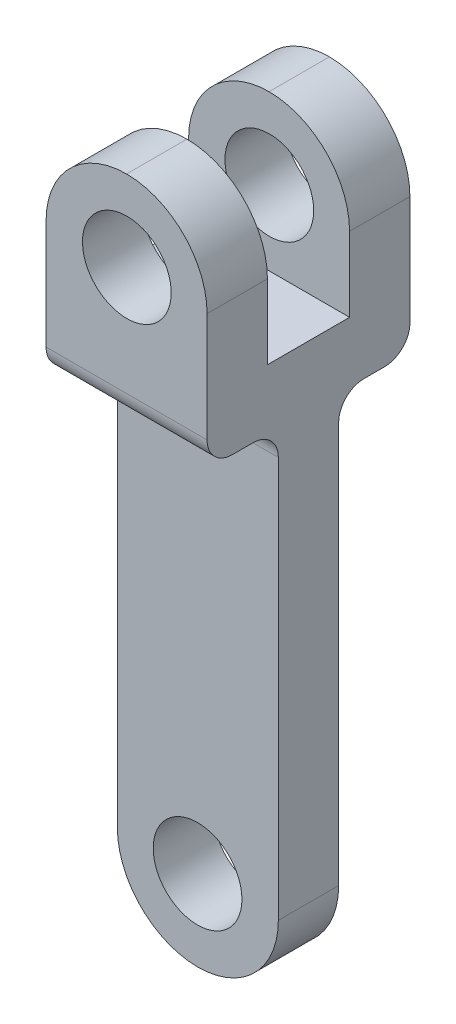
SolidWorks part; units mm, degrees
material "Alumina"
ref_plane "Plano frontal" through (0, 0, 0) normal (0, 0, 1) x (1, 0, 0)
ref_plane "Plano superior" through (0, 0, 0) normal (0, 1, 0) x (1, 0, 0)
ref_plane "Plano direito" through (0, 0, 0) normal (1, 0, 0) x (0, 0, -1)
sketch "Esboço2" plane through (0, 0, 0) normal (1, 0, 0) x (0, 0, -1)
  line L0 (8, 17) -> (8, 0)
  line L1 (8, 0) -> (-8, 0)
  line L2 (0, 0) -> (0, 13.3613) construction
  line L3 (-8, 17) -> (-8, 0)
  dimension "D1" = 17
  dimension "D2" = 8
extrude "Extrusão-Fina1" add sketch "Esboço2" along normal mid plane 12.7 thin thin type one direction reverse wall 4.76
fillet "Filete1" radius 6.37 4 edges at (-6.35, 17, -5.62) (-6.35, 17, 5.62) (6.35, 17, 5.62) (6.35, 17, -5.62)
sketch "Esboço3" plane through (0, 0, -8) normal (0, 0, -1) x (-1, 0, 0)
  circle A0 centre (-0.02, 10.63) radius 3.5
  dimension "D1" = 7
extrude "Corte-extrusão1" cut sketch "Esboço3" against normal through all
sketch "Esboço4" plane through (0, 0, 0) normal (0, -1, 0) x (1, 0, 0)
  line L0 (-6.35, 0) -> (6.35, 0)
  line L1 (-6.35, 8) -> (-6.35, -8) construction
  line L2 (6.35, 8) -> (6.35, -8) construction
extrude "Extrusão-Fina2" add sketch "Esboço4" along normal blind 40 thin thin type mid plane wall 4.76
fillet "Filete2" radius 6.37 2 edges at (-6.35, -40, 0) (6.35, -40, 0)
sketch "Esboço5" plane through (0, 0, 2.38) normal (0, 0, 1) x (1, 0, 0)
  circle A0 centre (-0.02, -33.63) radius 3.5
  dimension "D1" = 7
extrude "Corte-extrusão2" cut sketch "Esboço5" against normal through all
fillet "Filete4" radius 2 4 edges at (0, 0, 2.38) (0, 0, 8) (0, 0, -2.38) (0, 0, -8)
